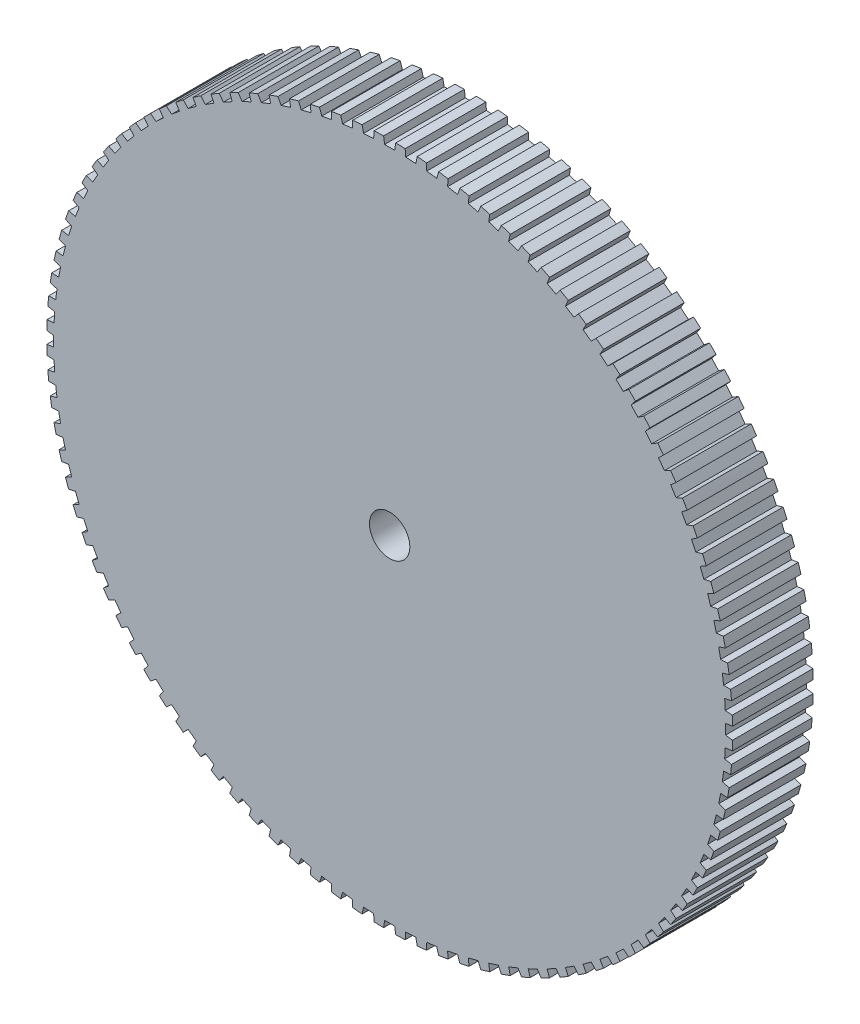
SolidWorks part; units mm, degrees
ref_plane "Front Plane" through (0, 0, 0) normal (0, 0, 1) x (1, 0, 0)
ref_plane "Top Plane" through (0, 0, 0) normal (0, 1, 0) x (1, 0, 0)
ref_plane "Right Plane" through (0, 0, 0) normal (1, 0, 0) x (0, 0, -1)
sketch "Sketch1" plane through (0, 0, 0) normal (0, 0, 1) x (1, 0, 0)
  circle A0 centre (0, 0) radius 37 construction
  circle A2 centre (0, 0) radius 34
  dimension "D1" = 74
  dimension "rubberthk" = 3
extrude "Boss-Extrude1" add sketch "Sketch1" along normal blind 8
sketch "Sketch4" plane through (0, 0, 0) normal (0, 0, -1) x (-1, 0, 0)
  circle A0 centre (0, 0) radius 4.85
  dimension "D1" = 9.7
extrude "Boss-Extrude2" add sketch "Sketch4" along normal blind 8
sketch "Sketch2" plane through (0, 0, 8) normal (0, 0, 1) x (1, 0, 0)
  circle A0 centre (0, 0) radius 4
  dimension "D1" = 8
extrude "Cut-Extrude1" cut sketch "Sketch2" against normal blind 4.35
sketch "Sketch5" plane through (0, 0, 3.65) normal (0, 0, 1) x (1, 0, 0)
  circle A0 centre (0, 0) radius 2
  dimension "D1" = 4
extrude "Cut-Extrude2" cut sketch "Sketch5" against normal offset from surface (4.15 mm away) 7.5 up to face at (-4.85, 0, -8)
sketch "Sketch6" plane through (0, 0, -8) normal (0, 0, -1) x (-1, 0, 0)
  line L0 (2.0785, 1.95) -> (-2.0785, 1.95)
  line L1 (-2.0785, -1.95) -> (2.0785, -1.95)
  arc A0 (2.0785, -1.95) -> (2.0785, 1.95) centre (0, 0) ccw
  arc A1 (-2.0785, 1.95) -> (-2.0785, -1.95) centre (0, 0) ccw
  dimension "D2" = 5.7
  dimension "D1" = 3.9
extrude "Cut-Extrude3" cut sketch "Sketch6" against normal up to surface (7.5 mm away) up to face at (-2, 0, -0.5)
sketch "Sketch7" plane through (0, 0, 8) normal (0, 0, 1) x (1, 0, 0)
  line L0 (-0.6, 33.9947) -> (-0.5, 33.31)
  line L1 (-0.5, 33.31) -> (0.5, 33.31)
  line L2 (0.5, 33.31) -> (0.6, 33.9947)
  line L3 (0, 0) -> (-0.6, 33.9947) construction
  line L4 (0, 0) -> (0.6, 33.9947) construction
  circle A0 centre (0, 0) radius 34 construction
  arc A1 (0.6, 33.9947) -> (-0.6, 33.9947) centre (0, 0) ccw
  point P8 (0, 33.31)
  dimension "D1" = 1
  dimension "D2" = 1.2
  dimension "D3" = 0.69
extrude "Cut-Extrude4" cut sketch "Sketch7" against normal through all
pattern_circular "CirPattern1" count 100 over 360 about axis through (0, 0, 8) along (0, 0, -1) of "Cut-Extrude4"
sketch "Sketch8" plane through (0, 0, 3.65) normal (0, 0, 1) x (1, 0, 0)
  circle A0 centre (0, 0) radius 2 construction
  circle A1 centre (0, 0) radius 4
  circle A2 centre (0, 0) radius 4
  circle A3 centre (0, 0) radius 2
  dimension "D1" = 0
extrude "ReverseCountersink" add sketch "Sketch8" along normal up to surface (4.35 mm away) up to face at (0, 0, 8)
equation "\"width\"= 24"
equation "\"thk\"= 3"
equation "\"holesize\"= 4.2"
equation "\"holedistance\"= ( 20 + 12 ) / 2"
equation "\"threaded_hole\"= 3.9"
equation "\"fillet_radius\"= 2"
equation "\"ground_clearance\"= 25"
equation "\"tire_thk\"= 3"
equation "\"innerwheel_diam\" = \"wheel_diam\"-2*\"tire_thk\""
equation "\"innerwheel_thk\"= 8"
equation "\"wheel_diam\"= 2*(\"width\"/2+\"ground_clearance\")"
equation "\"rubberthk@Sketch1\"=\"tire_thk\""
equation "\"D1@Boss-Extrude1\"=\"innerwheel_thk\""
equation "\"coloursensor_holesize\"= 2.65"
equation "\"hole_to_edge\" = 4"
equation "\"D1@Sketch1\"=\"wheel_diam\""
